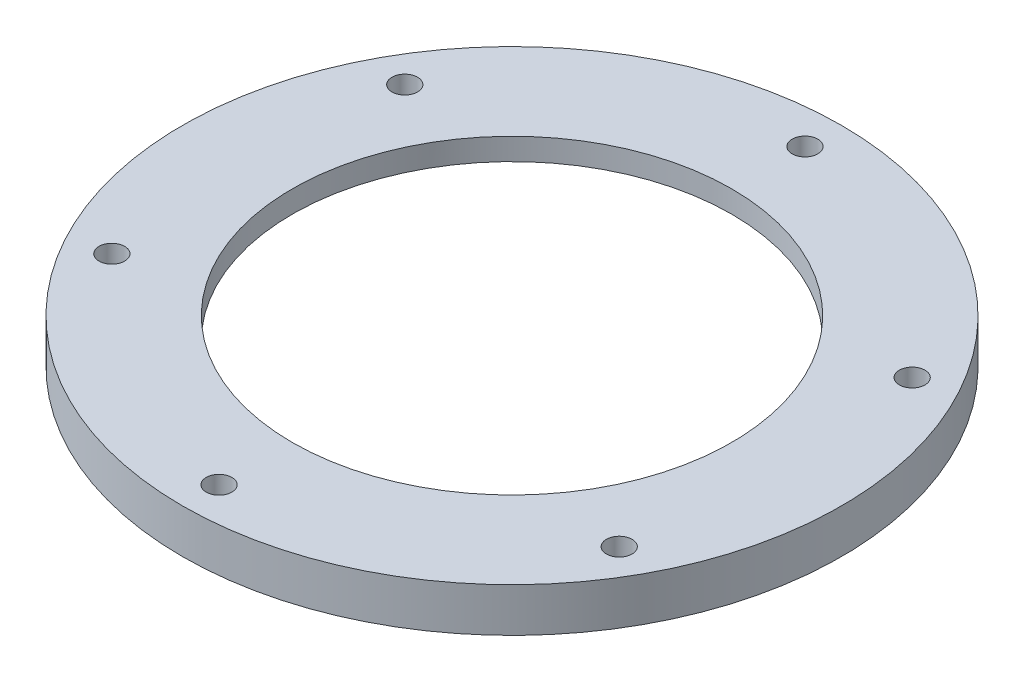
SolidWorks part; units mm, degrees
ref_plane "Front Plane" through (0, 0, 0) normal (0, 0, 1) x (1, 0, 0)
ref_plane "Top Plane" through (0, 0, 0) normal (0, 1, 0) x (1, 0, 0)
ref_plane "Right Plane" through (0, 0, 0) normal (1, 0, 0) x (0, 0, -1)
sketch "Sketch1" plane through (0, 0, 0) normal (0, 1, 0) x (1, 0, 0)
  line L0 (0, 0) -> (0, 52.0165) construction
  circle A0 centre (0, 0) radius 45
  circle A1 centre (0, 0) radius 30
  circle A2 centre (0, 0) radius 40 construction
  circle A3 centre (0, 40) radius 1.75
  circle A4 centre (0, 0) radius 36 construction
  circle A5 centre (34.641, 20) radius 1.75
  circle A6 centre (34.641, -20) radius 1.75
  circle A7 centre (0, -40) radius 1.75
  circle A8 centre (-34.641, -20) radius 1.75
  circle A9 centre (-34.641, 20) radius 1.75
  point P21 (0, 0)
  point P48 (0, 0)
  point P72 (0, 0)
  dimension "D1" = 90
  dimension "D2" = 60
  dimension "D4" = 3.5
  dimension "D5" = 72
  dimension "D6" = 6
  dimension "D3" = 80
extrude "Boss-Extrude1" add sketch "Sketch1" along normal blind 6
sketch "Sketch2" plane through (0, 0, 0) normal (0, -1, 0) x (1, 0, 0)
  circle A0 centre (0, 0) radius 36
  dimension "D1" = 72
extrude "Cut-Extrude1" cut sketch "Sketch2" against normal blind 3
